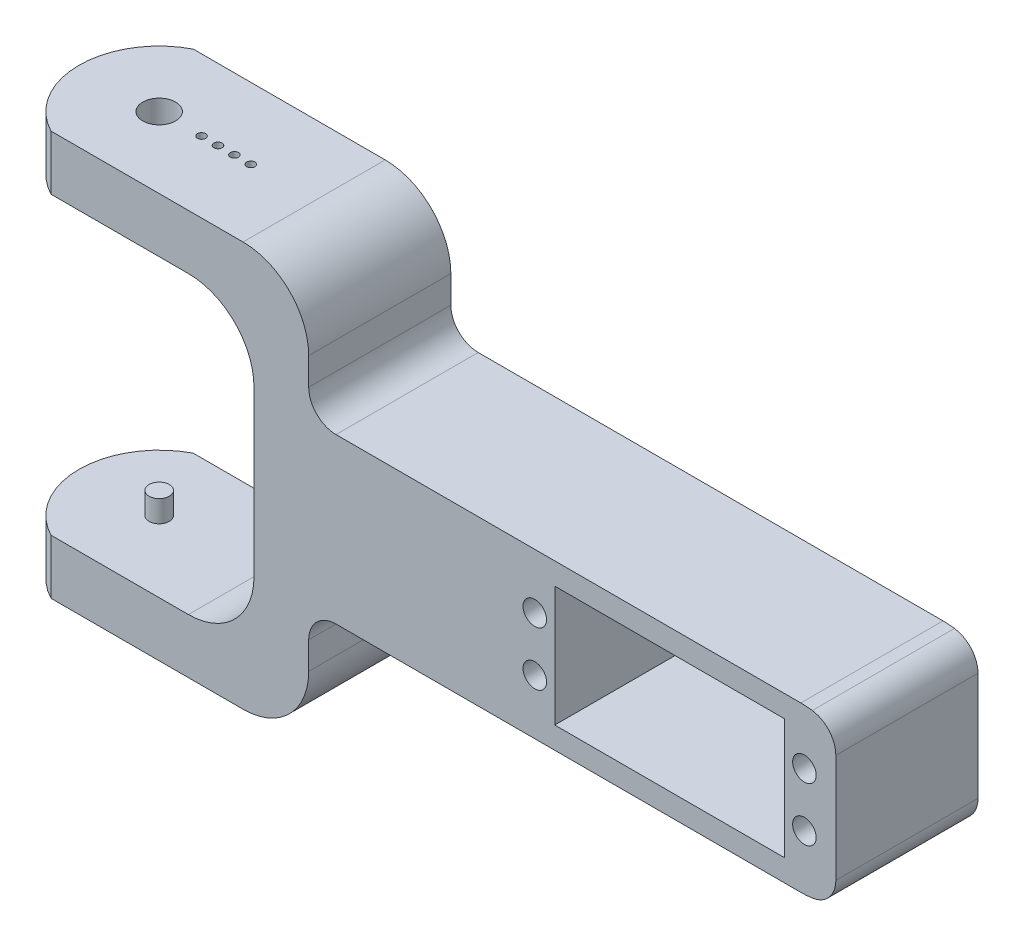
SolidWorks part; units mm, degrees
ref_plane "Plan de face" through (0, 0, 0) normal (0, 0, 1) x (1, 0, 0)
ref_plane "Plan de dessus" through (0, 0, 0) normal (0, 1, 0) x (1, 0, 0)
ref_plane "Plan de droite" through (0, 0, 0) normal (1, 0, 0) x (0, 0, -1)
sketch "Esquisse1" plane through (0, 0, 0) normal (0, 0, 1) x (1, 0, 0)
  line L1 (45, -15) -> (-45, -15)
  line L3 (45, 15) -> (-45, 15)
  line L4 (-45, -15) -> (-45, 15)
  line L5 (45, -15) -> (-45, 15) construction
  line L6 (45, 15) -> (-45, -15) construction
  arc A0 (45, -15) -> (45, 15) centre (45, 0) ccw
  point P0 (0, 0)
  dimension "D1" = 90
  dimension "D2" = 30
extrude "Boss.-Extru.1" add sketch "Esquisse1" along normal blind 26
sketch "Esquisse2" plane through (0, 0, 26) normal (0, 0, 1) x (1, 0, 0)
  line L0 (-45, 15) -> (-45, -15) construction
  line L1 (0, 11) -> (42, 11)
  line L2 (0, 11) -> (0, -11)
  line L3 (0, -11) -> (42, -11)
  line L4 (42, 11) -> (42, -11)
  point P4 (0, 0)
  dimension "D1" = 42
  dimension "D2" = 22
  dimension "D3" = 45
extrude "Enlèv. mat.-Extru.1" cut sketch "Esquisse2" against normal through all
ref_plane "Plan1" through (0, 0, 13) normal (0, 0, 1) x (1, 0, 0)
sketch "Esquisse9" plane through (0, 0, 13) normal (0, 0, 1) x (1, 0, 0)
  line L0 (-45, -37) -> (-45, 37)
  line L1 (-45, 37) -> (-100, 37)
  line L2 (-100, 37) -> (-100, 27)
  line L3 (-100, 27) -> (-55, 27)
  line L4 (-55, 27) -> (-55, -27)
  line L5 (-21.7036, 0) -> (-118.5775, 0) construction
  line L6 (-100, -27) -> (-55, -27)
  line L7 (-45, -37) -> (-100, -37)
  line L8 (-100, -37) -> (-100, -27)
  line L10 (-45, 15) -> (-45, -15) construction
  point P9 (-45, 0)
  point P10 (-55, 0)
  point P12 (-45, 0)
  dimension "D1" = 27
  dimension "D2" = 10
  dimension "D3" = 10
  dimension "D4" = 55
extrude "Boss.-Extru.2" add sketch "Esquisse9" along normal up to surface (13 mm away) and the other way up to surface (13 mm away) up to face at (21, 0, 26) other way up to face at (21, 0, 0)
sketch "Esquisse11" plane through (0, -37, 0) normal (0, -1, 0) x (1, 0, 0)
  line L0 (-100, 0) -> (-100, 26)
  line L1 (-100, 0) -> (-104.4348, 0)
  line L2 (-100, 26) -> (-104.4348, 26)
  arc A1 (-104.4348, 0) -> (-104.4348, 26) centre (-104.4348, 13) cw
extrude "Boss.-Extru.4" [suppressed] add sketch "Esquisse11" against normal blind 5
sketch "Esquisse17" [suppressed] plane through (0, -38, 0) normal (0, -1, 0) x (1, 0, 0)
  circle A2 centre (-95.3147, 7.5834) radius 4.5
  arc A3 (-104.4348, 17.5) -> (-104.4348, 2.5) centre (-104.4348, 10) ccw construction
  dimension "D1" = 9
  dimension "D2" = 9.4348
extrude "Enlèv. mat.-Extru.5" [suppressed] cut sketch "Esquisse17" against normal through all
sketch "Sketch1" plane through (0, -37, 0) normal (0, -1, 0) x (1, 0, 0)
  line L2 (-100, 0) -> (-100, 26) construction
  line L3 (-100, 26) -> (-45, 26) construction
  line L4 (-100, 0) -> (-45, 0) construction
  line L5 (-78.5501, 26) -> (-100, 26)
  line L6 (-100, 26) -> (-100, 13)
  line L7 (-100, 13) -> (-100, 0)
  line L8 (-100, 0) -> (-78.5501, 0)
  arc A0 (-78.5501, 26) -> (-78.5501, 0) centre (-85.3356, 13) ccw
  circle A1 centre (-85.3356, 13) radius 1.25
  line M2 (-45, 26) -> (-100, 26)
  line M3 (-100, 26) -> (-100, 0)
  line M4 (-100, 0) -> (-45, 0)
  dimension "D1" = 2.5
extrude "Cut-Extrude1" cut sketch "Sketch1" against normal through all contours A0 M3 M4 | A0 M2 M3 region at (-97.8069, -37, 3.0506) region at (-97.8069, -37, 22.9494)
fillet "Fillet1" radius 12 4 edges at (-45, 37, 13) (-45, -37, 13) (-55, 27, 13) (-55, -27, 13)
sketch "Sketch5" plane through (0, 27, 0) normal (0, -1, 0) x (1, 0, 0)
  circle A0 centre (-85.3356, 13) radius 3
  circle A1 centre (-77.5856, 13) radius 0.75
  circle A2 centre (-74.5856, 13) radius 0.75
  circle A3 centre (-71.5856, 13) radius 0.75
  circle A4 centre (-68.5856, 13) radius 0.75
extrude "Cut-Extrude3" cut sketch "Sketch5" against normal through all
sketch "Sketch6" plane through (0, -27, 0) normal (0, 1, 0) x (1, 0, 0)
  circle A0 centre (-85.3356, -13) radius 1.85
  dimension "D1" = 3.7
extrude "Boss-Extrude2" add sketch "Sketch6" along normal blind 4
sketch "Sketch7" plane through (0, 0, 26) normal (0, 0, 1) x (1, 0, 0)
  circle A0 centre (-3.65, 4.935) radius 2.15
  circle A1 centre (-3.65, -4.935) radius 2.15
  circle A2 centre (45.65, -4.935) radius 2.15
  circle A3 centre (45.65, 4.935) radius 2.15
extrude "Cut-Extrude4" cut sketch "Sketch7" against normal blind 15
fillet "Fillet2" radius 5 2 edges at (-45, 15, 13) (-45, -15, 13)
sketch "Sketch8" plane through (0, 0, 26) normal (0, 0, 1) x (1, 0, 0)
  line L0 (51.4017, 13.5653) -> (51.4017, -13.5653)
  line L1 (-40, -15) -> (45, -15) construction
  arc A0 (45, -15) -> (45, 15) centre (45, 0) ccw construction
  arc A1 (51.4017, -13.5653) -> (51.4017, 13.5653) centre (45, 0) ccw
extrude "Cut-Extrude5" cut sketch "Sketch8" against normal up to surface (26 mm away) up to face at (21, 0, 0)
fillet "Fillet3" radius 5 2 edges at (51.4017, -13.5653, 13) (51.4017, 13.5653, 13)
